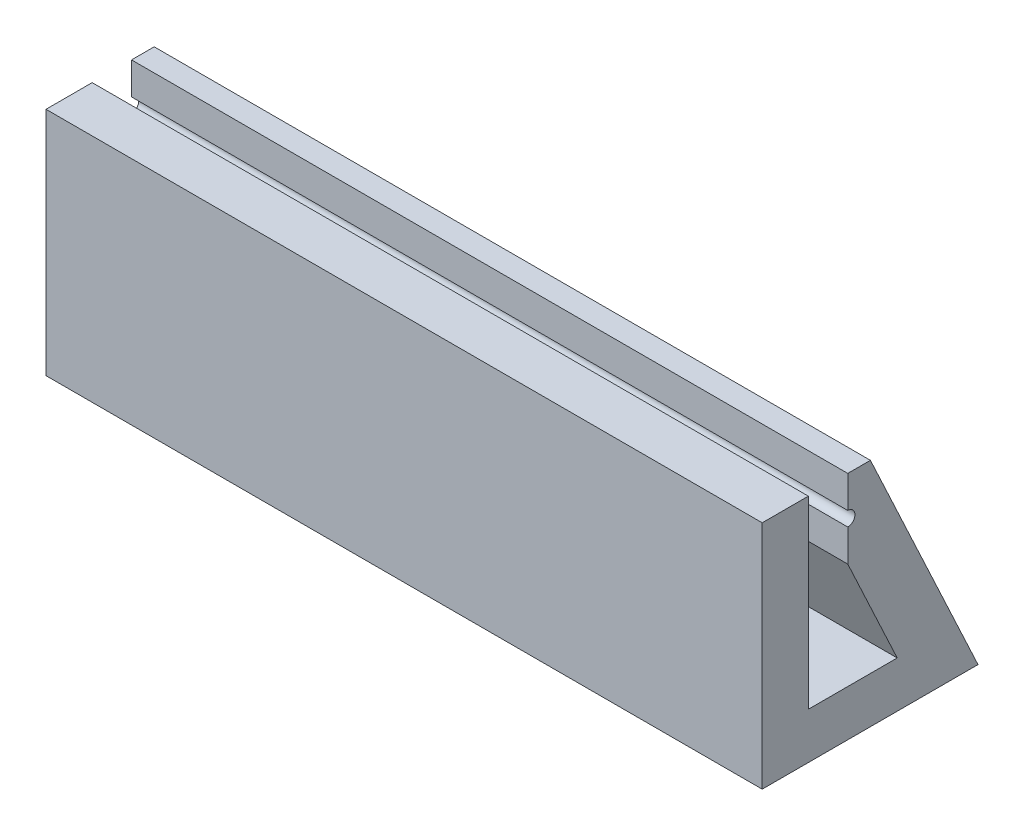
SolidWorks part; units mm, degrees
ref_plane "Front Plane" through (0, 0, 0) normal (0, 0, 1) x (1, 0, 0)
ref_plane "Top Plane" through (0, 0, 0) normal (0, 1, 0) x (1, 0, 0)
ref_plane "Right Plane" through (0, 0, 0) normal (1, 0, 0) x (0, 0, -1)
sketch "Sketch1" plane through (0, 0, 0) normal (1, 0, 0) x (0, 0, -1)
  line L0 (0, 0) -> (6.0256, 0)
  line L1 (0, 3.8658) -> (1.2888, 3.8658) construction
  line L2 (2.3888, 6.4428) -> (2.3888, 4.2499) construction
  line L3 (2.3888, 4.2499) -> (3.7696, 1.2888)
  line L4 (3.7696, 1.2888) -> (1.2888, 1.2888)
  line L5 (1.2888, 1.2888) -> (1.2888, 6.4428)
  line L6 (1.2888, 6.4428) -> (0, 6.4428)
  line L7 (0, 6.4428) -> (0, 0)
  line L8 (2.3888, 6.4428) -> (2.3888, 5.5463)
  line L9 (2.3888, 5.1463) -> (2.3888, 4.2499)
  line L10 (2.3888, 6.4428) -> (3.0213, 6.4428)
  line L11 (3.0213, 6.4428) -> (6.0256, 0)
  line L12 (2.5292, 1.2888) -> (2.5292, 0) construction
  arc A0 (2.3888, 5.5463) -> (2.3888, 5.1463) centre (2.3888, 5.3463) cw
  point P17 (0, 0)
  dimension "D1" = 0.2
  dimension "D2" = 1.1
  dimension "D3" = 65
  dimension "D4" = 1.5
extrude "Boss-Extrude1" add sketch "Sketch1" along normal mid plane 20 contours L8 A0 L9 L3 L4 L5 L6 L7 L0 L11 L10
